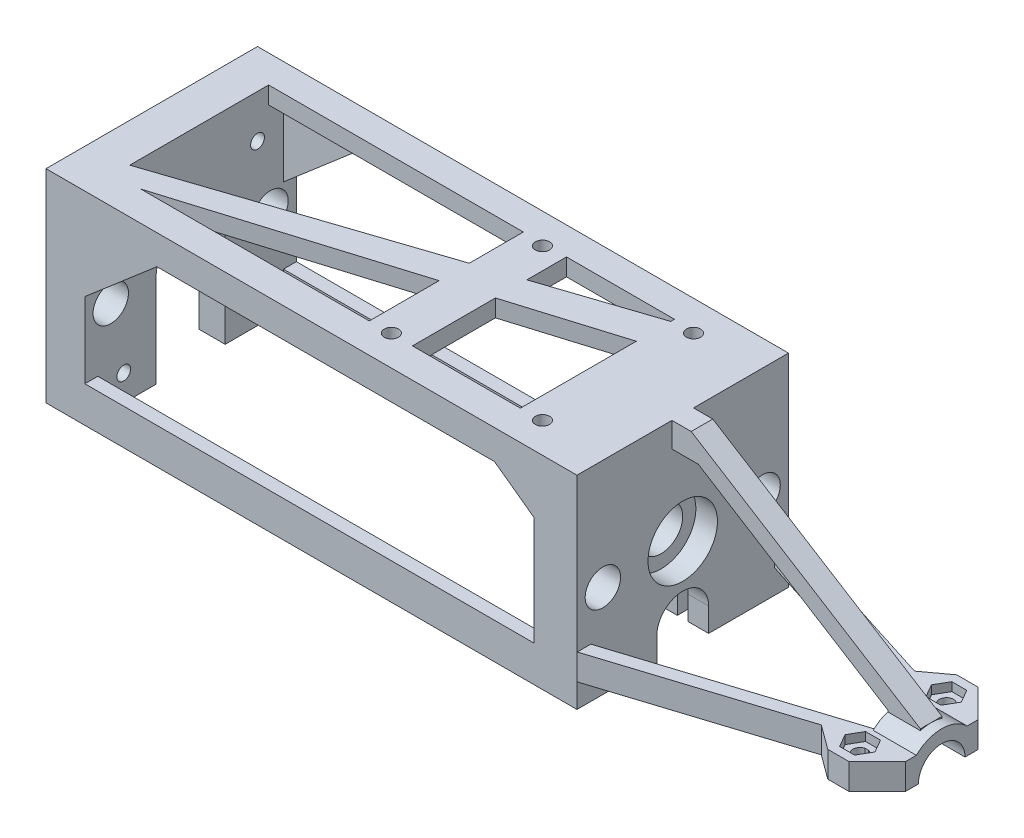
SolidWorks part; units mm, degrees
ref_plane "Front Plane" through (0, 0, 0) normal (0, 0, 1) x (1, 0, 0)
ref_plane "Top Plane" through (0, 0, 0) normal (0, 1, 0) x (1, 0, 0)
ref_plane "Right Plane" through (0, 0, 0) normal (1, 0, 0) x (0, 0, -1)
sketch "Sketch1" plane through (0, 0, 0) normal (0, 1, 0) x (1, 0, 0)
  line L0 (-61.5, 41.2067) -> (-25.5, 41.2067) construction
  line L1 (-61.5, -21.5) -> (61.5, -21.5)
  line L2 (-61.5, -21.5) -> (-61.5, 21.5)
  line L3 (-61.5, 21.5) -> (61.5, 21.5)
  line L4 (61.5, -21.5) -> (61.5, 21.5)
  line L5 (-61.5, -21.5) -> (61.5, 21.5) construction
  line L6 (-61.5, 21.5) -> (61.5, -21.5) construction
  line L7 (-61.5, 21.5) -> (-76.8616, 21.5)
  line L8 (-61.5, 21.5) -> (-61.5, -21.5)
  line L9 (-61.5, -21.5) -> (-76.8616, -21.5)
  line L11 (-61.5, -21.5) -> (-52.5, -21.5)
  line L12 (-61.5, -21.5) -> (-61.5, 21.5)
  line L13 (-61.5, 21.5) -> (-52.5, 21.5)
  line L14 (-52.5, -21.5) -> (-52.5, 21.5)
  line L15 (51.5, 21.5) -> (61.5, 21.5)
  line L16 (51.5, 21.5) -> (51.5, -21.5)
  line L17 (51.5, -21.5) -> (61.5, -21.5)
  line L18 (61.5, 21.5) -> (61.5, -21.5)
  line L19 (-25.5, 41.2067) -> (-10.5, 41.2067) construction
  line L20 (-10.5, 41.2067) -> (51.5, 41.2067) construction
  line L27 (-52.5, 18.0743) -> (-52.5, -14.0992)
  line L28 (-52.5, -14.0992) -> (44.0875, 18.0743)
  line L29 (44.0875, 18.0743) -> (-52.5, 18.0743)
  line L30 (-46.4258, -17.6087) -> (51.5, -17.6087)
  line L31 (51.5, -17.6087) -> (51.5, 12.3077)
  line L32 (51.5, 12.3077) -> (-46.4258, -17.6087)
  line L33 (0, 0) -> (16.5, 0) construction
  line L34 (51.5, 21.5) -> (41.5, 21.5)
  line L35 (51.5, 21.5) -> (51.5, -21.5)
  line L36 (51.5, -21.5) -> (41.5, -21.5)
  line L37 (41.5, 21.5) -> (41.5, -21.5)
  line L38 (16.5, 21.5) -> (6.5, 21.5)
  line L39 (16.5, 21.5) -> (16.5, -21.5)
  line L40 (16.5, -21.5) -> (6.5, -21.5)
  line L41 (6.5, 21.5) -> (6.5, -21.5)
  line L42 (41.5, 0) -> (51.5, 0) construction
  line L43 (6.5, 1.4647) -> (16.5, 1.4647) construction
  circle A0 centre (46.5, 17.5) radius 1.65
  circle A1 centre (11.5, 17.5) radius 1.65
  circle A2 centre (46.5, -17.5) radius 1.65
  circle A3 centre (11.5, -17.5) radius 1.65
  point P0 (0, 0)
  point P40 (46.5, 0)
  point P41 (11.5, 1.4647)
  dimension "D2" = 3.3
  dimension "D1" = 43
  dimension "D3" = 9
  dimension "D4" = 10
  dimension "D5" = 35
  dimension "D6" = 123
  dimension "D7" = 36
  dimension "D8" = 15
  dimension "D9" = 62
  dimension "D10" = 35
  dimension "D11" = 10
  dimension "D12" = 10
extrude "Boss-Extrude1" add sketch "Sketch1" along normal blind 4 contours L41 L28 L14 L1 L30 L32 | L1 L14 L3 L2 | L41 L3 L14 L29 | A1 L29 L39 L3 L41 | A1 L29 L41 L28 L39 | L28 L41 L32 L39 | L30 A3 L39 L32 L41 | L30 A3 L41 L1 L39 | L30 A2 L37 L1 L16 | L30 L39 L1 L37 | L30 A2 L16 L32 L37 | A0 L28 L37 L32 L16 L3 L29 | L28 L39 L32 L37 | L3 L39 L29 L37 | A0 L29 L37 L28 | L3 L16 L1 L4 region at (-57, 0, 0) region at (-51.8509, 0, 17.7996) region at (11.5, 0, 19.6993) region at (-23, 0, -19.7872) region at (29, 0, 19.5543) region at (11.6477, 0, 8.5201) region at (11.229, 0, -12.3352) region at (11.5323, 0, -3.6638) region at (11.5, 0, -19.8835) region at (46.5, 0, 19.6993) region at (29.1888, 0, -9.3016) region at (29, 0, -19.7872) region at (56.5, 0, 0) region at (46.5912, 0, 3.1772) region at (42.3625, 0, -17.787) region at (42.8437, 0, -17.4934)
extrude "Boss-Extrude2" add sketch "Sketch1<3>" against normal blind 43 contours L3 L2 L1 | L3 L16 L1 L4 region at (-57, 0, 0) region at (56.5, 0, 0)
sketch "Sketch1<3>" plane through (0, 0, 0) normal (0, 1, 0) x (1, 0, 0) same geometry as "Sketch1"
sketch "Sketch3" plane through (-52.5, 0, 0) normal (1, 0, 0) x (0, 0, -1)
  line L0 (-21.5, -43) -> (21.5, -43) construction
  line L1 (-15.5, -6) -> (15.5, -6) construction
  line L2 (-15.5, -6) -> (-15.5, -37) construction
  line L3 (-15.5, -37) -> (15.5, -37) construction
  line L4 (15.5, -6) -> (15.5, -37) construction
  line L5 (-15.5, -6) -> (15.5, -37) construction
  line L6 (-15.5, -37) -> (15.5, -6) construction
  line L7 (21.5, -43) -> (21.5, 0) construction
  line L8 (-18.5, -21.5) -> (18.5, -21.5) construction
  line L9 (8, -43) -> (8, -21.5)
  line L10 (-8, -43) -> (-8, -21.5)
  circle A0 centre (18.5, -21.5) radius 4.1
  circle A1 centre (-18.5, -21.5) radius 4.1
  circle A2 centre (15.5, -37) radius 1.6
  circle A3 centre (15.5, -6) radius 1.6
  circle A4 centre (-15.5, -6) radius 1.6
  circle A5 centre (-15.5, -37) radius 1.6
  circle A6 centre (0, -21.5) radius 8
  point P4 (0, -21.5)
  point P12 (0, -21.5)
  point P17 (0, -43)
  point P21 (21.5, -21.5)
  line M14 (-21.5, -43) -> (21.5, -43)
  dimension "D1" = 3.2
  dimension "D3" = 8.2
  dimension "D5" = 16
  dimension "D2" = 31
  dimension "D4" = 37
extrude "Cut-Extrude2" cut sketch "Sketch3" against normal blind 43 contours A2 | A6 | A6 L10 L9 M14 | A0 | A3 | A4 | A1 | A5 region at (-52.5, -35.2868, 0) region at (-52.5, -21.5, 0) region at (-52.5, -21.5, -18.5) region at (-52.5, -21.5, 18.5) region at (-52.5, -37, -15.5) region at (-52.5, -6, -15.5) region at (-52.5, -6, 15.5) region at (-52.5, -37, 15.5)
sketch "Sketch4" plane through (61.5, 0, 0) normal (1, 0, 0) x (0, 0, -1)
  line L0 (18.5, -21.5) -> (-18.5, -21.5) construction
  line L1 (-21.5, -43) -> (21.5, -43) construction
  line L2 (21.5, 4) -> (21.5, -43) construction
  line L3 (6, -37.5) -> (6, -43)
  line L4 (-6, -37.5) -> (-6, -43)
  line L7 (21.5, -43) -> (21.5, 0)
  circle A0 centre (18.5, -21.5) radius 4.1
  circle A1 centre (-18.5, -21.5) radius 4.1
  circle A2 centre (0, -21.5) radius 8.05
  circle A3 centre (0, -21.5) radius 5
  arc A4 (6, -37.5) -> (-6, -37.5) centre (0, -37.5) ccw
  point P4 (0, -21.5)
  point P7 (0, -43)
  point P24 (21.5, -21.5)
  point P27 (0, 0)
  line M5 (-21.5, 4) -> (-21.5, -43)
  line M6 (-21.5, -43) -> (21.5, -43)
  dimension "D1" = 8.2
  dimension "D3" = 16.1
  dimension "D4" = 10
  dimension "D5" = 6
  dimension "D2" = 37
  dimension "D6" = 16
extrude "Cut-Extrude3" cut sketch "Sketch4" against normal blind 43 contours L3 A4 L4 M6 | A3 L0 | L0 A3 | A0 | A1 region at (61.5, -37.806, 0) region at (61.5, -17.7858, -17.0381) region at (61.5, -21.5, 22.484) region at (61.5, -23.6221, 0) region at (61.5, -19.3779, 0)
extrude "Cut-Extrude4" cut sketch "Sketch4<3>" against normal blind 5 contours A2 L0 A3 | L0 A2 A3 region at (61.5, -29.37, 0) region at (61.5, -21.32, -6.525)
sketch "Sketch4<3>" plane through (61.5, 0, 0) normal (1, 0, 0) x (0, 0, -1) same geometry as "Sketch4"
sketch "Sketch6" plane through (0, 0, -21.5) normal (0, 0, -1) x (-1, 0, 0)
  line L2 (61.5, -43) -> (52.5, -43)
  line L3 (52.5, -43) -> (-51.5, -43)
  line L4 (-51.5, -43) -> (-61.5, -43)
  line L5 (-61.5, -43) -> (-61.5, 4)
  line L6 (-61.5, 4) -> (61.5, 4)
  line L33 (52.5, -34.6566) -> (-51.5, -34.6566)
  line L34 (52.5, -34.6566) -> (52.5, -2.8265)
  line L35 (52.5, -2.8265) -> (-51.5, -2.8265)
  line L36 (-51.5, -34.6566) -> (-51.5, -2.8265)
  line L37 (52.5, -43) -> (52.5, -24.2946) construction
  line L44 (-51.5, -43) -> (-61.5, -43) construction
  line L45 (-51.5, -43) -> (-51.5, -24.2946) construction
  line L46 (61.5, 4) -> (-61.5, 4) construction
  line L47 (61.5, 4) -> (61.5, -43)
  line L48 (-51.5, -18.7054) -> (-51.5, 0) construction
  line L49 (35.8171, -2.8265) -> (52.5, -17.1677)
  line L50 (-42.4071, -2.8265) -> (-51.5, -9.424)
  line M2 (-51.5, -18.7054) -> (-51.5, 0)
  line M4 (52.5, 0) -> (52.5, -18.7054)
  line M7 (-51.5, 0) -> (52.5, 0)
  line M10 (61.5, -18.7054) -> (61.5, 4)
  line M11 (61.5, 4) -> (-61.5, 4)
  line M12 (-61.5, 4) -> (-61.5, -18.7054)
  line M53 (52.5, -18.7054) -> (61.5, -18.7054)
  line M55 (-61.5, -18.7054) -> (-51.5, -18.7054)
extrude "Boss-Extrude3" add sketch "Sketch6" along normal blind 3 contours L47 L34 L33 L36 L5 L4 L3 L2 M53 M55 | L36 L34 M12 M55 M2 M7 M4 M53 M10 M11 | L35 M4 M7 M2 | L35 L49 M4 | L50 L35 L36 region at (0.624, -36.0588, -21.5) region at (-57, -17.4546, -21.5) region at (-46.939, -7.6069, -21.5) region at (-0.5, -1.4132, -21.5) region at (48.469, -5.0256, -21.5)
mirror "Mirror1" about plane through (0, 0, 0) normal (0, 0, 1) of "Boss-Extrude3"
ref_plane "Plane1" through (55.5, 0, 0) normal (1, 0, 0) x (0, 0, -1)
sketch "Sketch7" plane through (55.5, 0, 0) normal (1, 0, 0) x (0, 0, -1)
  line L0 (11.7097, -33.5) -> (1.4432, -31.1622)
  line L1 (0, -37.5) -> (0, -36.259) construction
  line L2 (12.5, -34.4905) -> (12.5, -59.658)
  line L3 (-12.5, -34.4905) -> (-12.5, -59.658)
  line L4 (-11.7097, -33.5) -> (-1.4432, -31.1622)
  line L5 (12.5, -59.658) -> (-12.5, -59.658)
  arc A0 (1.4432, -31.1622) -> (-1.4432, -31.1622) centre (0, -37.5) ccw
  arc A1 (6, -37.5) -> (-6, -37.5) centre (0, -37.5) ccw construction
  arc A2 (11.7097, -33.5) -> (12.5, -34.4905) centre (11.4841, -34.4905) cw
  arc A3 (-11.7097, -33.5) -> (-12.5, -34.4905) centre (-11.4841, -34.4905) ccw
  dimension "D1" = 6.5
  dimension "D2" = 25
  dimension "D3" = 4
extrude "Cut-Extrude6" cut sketch "Sketch7" against normal mid plane 2.5 contours L4 A3 L3 L5 L2 A2 L0 A0 region at (55.5, -45.9532, 0)
sketch "Sketch8" plane through (-61.5, 0, 0) normal (-1, 0, 0) x (0, 0, 1)
  line L0 (-11.5, -21.5) -> (-11.5, -43)
  line L1 (-8, -43) -> (-24.5, -43) construction
  line L2 (11.5, -21.5) -> (11.5, -43)
  line L3 (24.5, -43) -> (8, -43) construction
  line L4 (11.5, -43) -> (-11.5, -43)
  circle A0 centre (0, -21.5) radius 11.5
  arc A2 (8, -21.5) -> (-8, -21.5) centre (0, -21.5) ccw construction
  arc M3 (-21.5, -18.7054) -> (-21.5, -24.2946) centre (-18.5, -21.5) cw
  arc M6 (21.5, -24.2946) -> (21.5, -18.7054) centre (18.5, -21.5) cw
  line M9 (-24.5, -43) -> (-8, -43)
  line M10 (-8, -43) -> (-8, -21.5)
  arc M11 (-8, -21.5) -> (8, -21.5) centre (0, -21.5) cw
  line M12 (8, -21.5) -> (8, -43)
  line M13 (8, -43) -> (24.5, -43)
  dimension "D1" = 23
extrude "Cut-Extrude7" cut sketch "Sketch8" against normal blind 3 contours A0 M10 M12 M11 | A0 M6 M3 M10 M11 M12 | A0 L0 M3 M9 M10 | A0 L2 M12 M13 M6 | A0 M3 | A0 M6 region at (-61.5, -34.9841, -9.8691) region at (-61.5, -10.3032, 0) region at (-61.5, -34.9841, 9.8691) region at (-61.5, -23.5345, 0)
extrude "Cut-Extrude9" cut sketch "Sketch4<4>" against normal blind 150 contours L7 A0 | A1 M5 | A1 M5 | L7 A0 region at (61.5, -21.5, -18.2005) region at (61.5, -21.5, -21.9455) region at (61.5, -21.5, 18.2005) region at (61.5, -21.5, 21.9455)
sketch "Sketch4<4>" plane through (61.5, 0, 0) normal (1, 0, 0) x (0, 0, -1) same geometry as "Sketch4"
sketch "Sketch10" plane through (61.5, 0, 0) normal (1, 0, 0) x (0, 0, -1)
  line L0 (8.4, -37.5) -> (5.4, -37.5)
  line L1 (-5.4, -37.5) -> (-8.4, -37.5)
  arc A0 (5.4, -37.5) -> (-5.4, -37.5) centre (0, -37.5) ccw
  arc A1 (8.4, -37.5) -> (-8.4, -37.5) centre (0, -37.5) ccw
  arc A3 (6, -37.5) -> (-6, -37.5) centre (0, -37.5) ccw construction
  dimension "D2" = 5.4
  dimension "D1" = 3
extrude "Boss-Extrude4" add sketch "Sketch10" along normal blind 60
extrude "Cut-Extrude10" cut sketch "Sketch10<2>" along normal blind 50
sketch "Sketch10<2>" plane through (61.5, 0, 0) normal (1, 0, 0) x (0, 0, -1) same geometry as "Sketch10"
sketch "Sketch12" plane through (0, 0, 0) normal (0, 0, 1) x (1, 0, 0)
  line L0 (111.5, -29.1) -> (61.5, 2.0649)
  line L1 (61.5, 2.0649) -> (61.5, 6.7782)
  line L2 (61.5, 6.7782) -> (119.062, -29.1)
  line L3 (119.062, -29.1) -> (111.5, -29.1)
  line L4 (65.9573, 4) -> (61.5, 4)
  line L5 (67.614, -1.746) -> (61.5, -1.746)
  line L7 (111.5, -29.1) -> (111.5, -30.1)
  line L8 (111.5, -30.1) -> (119.062, -30.1)
  line L9 (119.062, -30.1) -> (119.062, -29.1)
  line L10 (61.5, -1.746) -> (61.5, 2.0649)
  point P3 (111.5, -29.1)
  point P5 (65.1321, 4)
  point P6 (121.5, -29.1)
  point P15 (111.5, -29.1)
  point P17 (65.9573, 4)
  dimension "D1" = 4
  dimension "D2" = 1
extrude "Boss-Extrude5" add sketch "Sketch12" along normal mid plane 5 contours L3 L2 L1 L0 | L8 L9 L3 L7 | L10 L5 L0 region at (89.072, -12.7432, 0) region at (115.281, -29.6, 0) region at (63.538, -0.4757, 0)
sketch "Sketch13" plane through (0, -37.5, 0) normal (0, -1, 0) x (1, 0, 0)
  line L0 (61.5, -21.2899) -> (61.5, -24.4378)
  line L1 (61.5, -24.4378) -> (121.4052, -5.4)
  line L2 (104.4084, -10.8015) -> (110.0403, -14.9391)
  line L3 (121.4052, -5.4) -> (111.5, -5.4)
  line L4 (111.5, -5.4) -> (61.5, -21.2899)
  line L5 (61.5, -6) -> (61.5, -24.5) construction
  line L6 (121.5, -5.4) -> (111.5, -5.4) construction
  line L7 (110.0403, -14.9391) -> (114.9439, -14.9391)
  line L8 (114.9439, -14.9391) -> (121.5, -8.4)
  line L9 (121.5, -8.4) -> (121.4052, -5.4)
  circle A0 centre (112.5748, -10) radius 1.65
  point P12 (0, 0)
  point P13 (0, 0)
  line M5 (121.5, -5.4) -> (111.5, -5.4)
  line M6 (111.5, -5.4) -> (111.5, -8.4)
  line M7 (111.5, -8.4) -> (121.5, -8.4)
  dimension "D2" = 3.3
  dimension "D1" = 3
  dimension "D3" = 10
extrude "Boss-Extrude6" add sketch "Sketch13" against normal blind 6 contours L4 L0 L1 M6 M7 | L9 L1 M7 | L1 M7 M5 M6 | L7 L8 L1 L2 A0 M7 region at (86.5055, -37.5, -14.9175) region at (114.8087, -37.5, -6.4449) region at (108.2423, -37.5, -9.7752) region at (118.3009, -37.5, -7.3981)
mirror "Mirror2" about plane through (0, 0, 0) normal (0, 0, 1) of "Boss-Extrude6"
sketch "Sketch14" plane through (61.5, 0, 0) normal (1, 0, 0) x (0, 0, -1)
  line L0 (0, 0) -> (0, -11.8181) construction
  line L1 (15.5, -35) -> (9.5, -35)
  line L2 (15.5, -35) -> (15.5, -40)
  line L3 (15.5, -40) -> (9.5, -40)
  line L4 (9.5, -35) -> (9.5, -40)
  line L5 (15.5, -35) -> (9.5, -40) construction
  line L6 (15.5, -40) -> (9.5, -35) construction
  line L7 (-15.5, -40) -> (-9.5, -40)
  line L8 (-9.5, -35) -> (-9.5, -40)
  line L9 (-15.5, -35) -> (-9.5, -35)
  line L10 (-15.5, -35) -> (-15.5, -40)
  arc A0 (6, -37.5) -> (-6, -37.5) centre (0, -37.5) ccw construction
  point P0 (12.5, -37.5)
  point P12 (0, -37.5)
  point P17 (12.5, -40)
  point P18 (-12.5, -40)
  dimension "D1" = 5
  dimension "D2" = 6
  dimension "D3" = 25
sketch "Sketch16" plane through (0, -37.5, 0) normal (0, -1, 0) x (1, 0, 0)
  line L1 (111.5, -5.4) -> (121.5, -5.4)
  line L2 (111.5, -5.4) -> (111.5, -8.4)
  line L3 (111.5, -8.4) -> (121.5, -8.4)
  line L4 (121.5, -5.4) -> (121.5, -8.4)
  line L5 (111.5, -5.4) -> (121.5, -8.4) construction
  line L6 (111.5, -8.4) -> (121.5, -5.4) construction
  line L7 (111.5, 5.4) -> (121.5, 5.4)
  line L8 (111.5, 5.4) -> (111.5, 8.4)
  line L9 (111.5, 8.4) -> (121.5, 8.4)
  line L10 (121.5, 5.4) -> (121.5, 8.4)
  line L11 (111.5, 5.4) -> (121.5, 8.4) construction
  line L12 (111.5, 8.4) -> (121.5, 5.4) construction
  point P0 (116.5, -6.9)
  point P8 (116.5, 6.9)
extrude "Boss-Extrude7" add sketch "Sketch16" against normal blind 6
sketch "Sketch17" plane through (0, -31.5, 0) normal (0, 1, 0) x (1, 0, 0)
  line L1 (114.3068, 7) -> (116.0389, 10)
  line L2 (116.0389, 10) -> (114.3068, 13)
  line L3 (114.3068, 13) -> (110.8427, 13)
  line L4 (110.8427, 13) -> (109.1107, 10)
  line L5 (109.1107, 10) -> (110.8427, 7)
  line L6 (110.8427, 7) -> (114.3068, 7)
  line L7 (116.0389, -10) -> (114.3068, -7)
  line L8 (114.3068, -7) -> (110.8427, -7)
  line L9 (110.8427, -7) -> (109.1107, -10)
  line L10 (109.1107, -10) -> (110.8427, -13)
  line L11 (110.8427, -13) -> (114.3068, -13)
  line L12 (114.3068, -13) -> (116.0389, -10)
  circle A0 centre (112.5748, 10) radius 3 construction
  circle A1 centre (112.5748, -10) radius 3 construction
  circle A2 centre (112.5748, 10) radius 1.65 construction
  circle A3 centre (112.5748, -10) radius 1.65 construction
  point P9 (0, 0)
  point P19 (0, 0)
  dimension "D1" = 6
extrude "Cut-Extrude12" cut sketch "Sketch17" against normal blind 2
chamfer "Chamfer1" distance 2 angle 45 rebuild error yes
